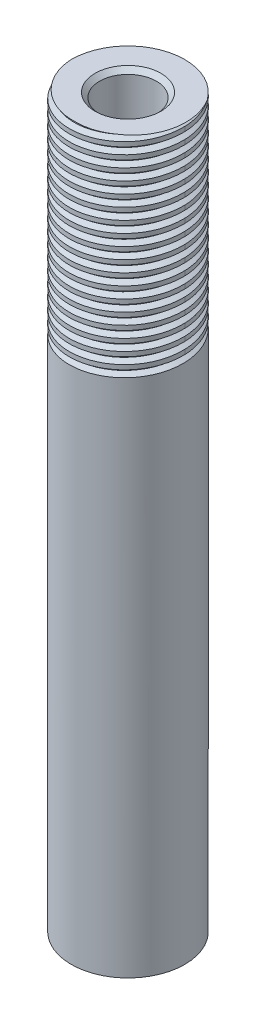
SolidWorks part; units mm, degrees
ref_plane "Front Plane" through (0, 0, 0) normal (0, 0, 1) x (1, 0, 0)
ref_plane "Top Plane" through (0, 0, 0) normal (0, 1, 0) x (1, 0, 0)
ref_plane "Right Plane" through (0, 0, 0) normal (1, 0, 0) x (0, 0, -1)
sketch "Эскиз1" plane through (0, 0, 0) normal (0, 0, 1) x (1, 0, 0)
  line L0 (0, 0) -> (0, 32) construction
  line L13 (0, 32) -> (2.5, 32)
  line L14 (0, 32) -> (0, 0)
  line L15 (0, 0) -> (2.5, 0)
  line L16 (2.5, 32) -> (2.5, 0)
  dimension "D1" = 2.5
  dimension "D2" = 32
revolve "Повернуть1" add sketch "Эскиз1" angle 360 about L0
thread "Резьба1" pitch 0.4 method cut profile "Thread Profile1" start angle 0, offset 1, length 10, pitch 0.5, diameter 5
ref_plane "Плоскость1" through (-2.5, 33, 0) normal (0, 0, -1) x (1, 0, 0)
sketch "Thread Profile1" plane through (-2.5, 33, 0) normal (0, 0, -1) x (1, 0, 0)
  line L0 (0, 0) -> (0, 0.4) construction
  line L1 (0, 0) -> (0.2165, 0.125)
  line L2 (0.2165, 0.125) -> (0.2165, 0.175)
  line L3 (0.2165, 0.175) -> (0, 0.3)
  line L4 (0.2165, 0.15) -> (0, 0.15) construction
  line L11 (0, 0) -> (0, 0.3)
  point P2 (0, 0)
  dimension "Pitch" = 0.4
  dimension "Profile_Angle" = 60
  dimension "Profile_Land" = 0.05
  dimension "Profile_Height" = 0.2165
sketch "Эскиз2" plane through (0, 32, 0) normal (0, 1, 0) x (1, 0, 0)
  circle A0 centre (0, 0) radius 1.25
  dimension "D1" = 2.5
extrude "Вырез-Вытянуть1" cut sketch "Эскиз2" against normal through all
chamfer "Фаска1" distance 0.2 angle 45 1 edges at (-1.25, 32, 0)
